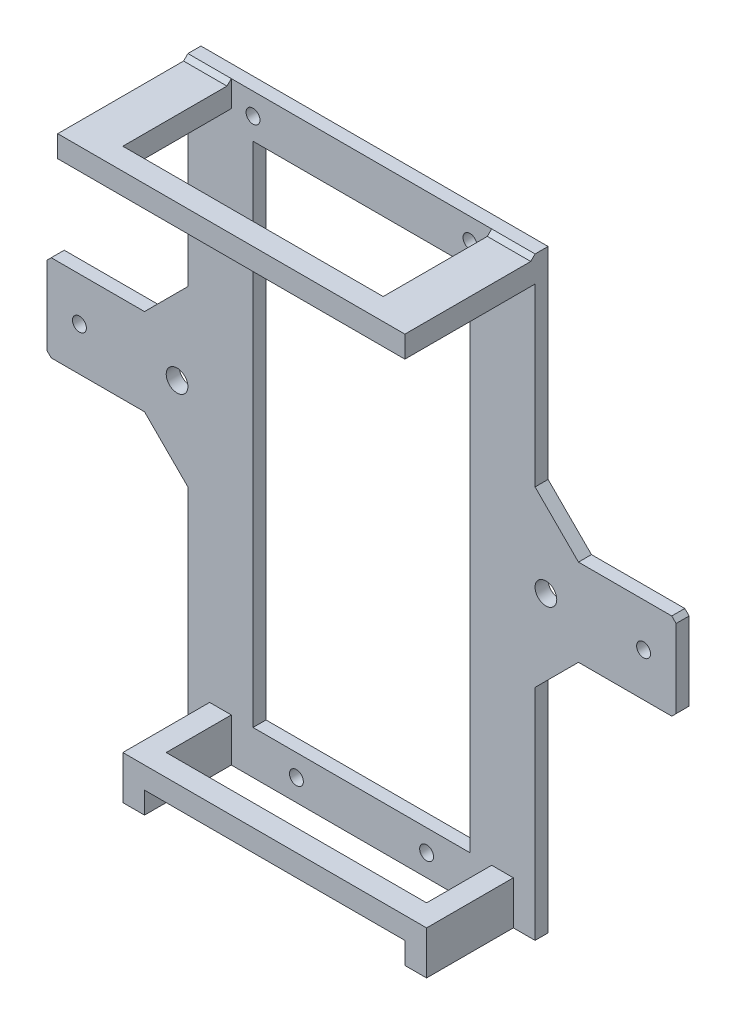
SolidWorks part; units mm, degrees
material "ABS"
ref_plane "前视基准面" through (0, 0, 0) normal (0, 0, 1) x (1, 0, 0)
ref_plane "上视基准面" through (0, 0, 0) normal (0, 1, 0) x (1, 0, 0)
ref_plane "右视基准面" through (0, 0, 0) normal (1, 0, 0) x (0, 0, -1)
other "Configuration Table"
sketch "草图9" plane through (0, 0, 0) normal (0, 0, 1) x (1, 0, 0)
  line L0 (-40, 66.5) -> (40, 66.5)
  line L1 (40, 66.5) -> (40, 10)
  line L2 (40, 10) -> (72.5, 10)
  line L3 (72.5, 10) -> (72.5, -10)
  line L4 (72.5, -10) -> (40, -10)
  line L5 (40, -10) -> (40, -70.5)
  line L6 (40, -70.5) -> (-40, -70.5)
  line L7 (0, 66.5) -> (0, -70.5) construction
  line L8 (-25, -60.5) -> (25, -60.5)
  line L9 (25, -60.5) -> (25, 56.5)
  line L10 (25, 56.5) -> (-25, 56.5)
  line L11 (-40, 61.5) -> (40, 61.5) construction
  line L12 (-40, -65.5) -> (40, -65.5) construction
  line L13 (72.5, 0) -> (-72.5, 0) construction
  line L14 (-25, -60.5) -> (-25, 56.5)
  line L15 (-40, -10) -> (-40, -70.5)
  line L16 (-72.5, -10) -> (-40, -10)
  line L17 (-72.5, 10) -> (-72.5, -10)
  line L18 (-40, 10) -> (-72.5, 10)
  line L19 (-40, 66.5) -> (-40, 10)
  circle A0 centre (25, 61.5) radius 1.6
  circle A1 centre (15, -65.5) radius 1.6
  circle A2 centre (42.5, 0) radius 2.5
  circle A3 centre (-42.5, 0) radius 2.5
  circle A4 centre (-15, -65.5) radius 1.6
  circle A5 centre (-25, 61.5) radius 1.6
  circle A6 centre (-65, 0) radius 1.6
  circle A7 centre (65, 0) radius 1.6
  point P26 (0, 0)
  point P27 (0, -65.5)
  point P28 (0, 61.5)
  point P35 (0, 56.5)
  point P36 (0, -60.5)
  dimension "D3" = 5
  dimension "D5" = 85
  dimension "D9" = 2.5
  dimension "D10" = 50
  dimension "D11" = 30
  dimension "D13" = 3.2
  dimension "D14" = 130
  dimension "D1" = 127
  dimension "D2" = 20
  dimension "D4" = 15
  dimension "D6" = 30
  dimension "D7" = 10
  dimension "D8" = 10
  dimension "D12" = 65.5
extrude "凸台-拉伸7" add sketch "草图9" along normal blind 3
sketch "草图10" plane through (0, 0, 3) normal (0, 0, 1) x (1, 0, 0)
  line L0 (0, 66.5) -> (0, 56.5) construction
  line L1 (-40, 65.5) -> (-30, 65.5)
  line L2 (-40, 65.5) -> (-40, 60.5)
  line L3 (-40, 60.5) -> (-30, 60.5)
  line L4 (-30, 65.5) -> (-30, 60.5)
  line L5 (40, 66.5) -> (-40, 66.5) construction
  line L6 (25, 56.5) -> (-25, 56.5) construction
  line L7 (40, 60.5) -> (30, 60.5)
  line L8 (30, 65.5) -> (30, 60.5)
  line L9 (40, 65.5) -> (30, 65.5)
  line L10 (40, 65.5) -> (40, 60.5)
  line L11 (-40, 66.5) -> (-40, 10) construction
  dimension "D1" = 10
  dimension "D2" = 5
  dimension "D3" = 1
extrude "凸台-拉伸8" add sketch "草图10" along normal blind 30
sketch "草图11" plane through (0, 0, 3) normal (0, 0, 1) x (1, 0, 0)
  line L1 (-35, -60.5) -> (-30, -60.5)
  line L2 (-35, -60.5) -> (-35, -70.5)
  line L3 (-35, -70.5) -> (-30, -70.5)
  line L4 (-30, -60.5) -> (-30, -70.5)
  line L5 (0, -60.5) -> (0, -70.5) construction
  line L6 (-25, -60.5) -> (25, -60.5) construction
  line L7 (-40, -70.5) -> (40, -70.5) construction
  line L8 (35, -70.5) -> (30, -70.5)
  line L9 (30, -60.5) -> (30, -70.5)
  line L10 (35, -60.5) -> (30, -60.5)
  line L11 (35, -60.5) -> (35, -70.5)
  dimension "D1" = 70
  dimension "D2" = 10
  dimension "D3" = 5
extrude "凸台-拉伸9" add sketch "草图11" along normal blind 20
sketch "草图12" plane through (0, 0, 33) normal (0, 0, 1) x (1, 0, 0)
  line L1 (-40, 65.5) -> (40, 65.5)
  line L2 (-40, 65.5) -> (-40, 60.5)
  line L3 (-40, 60.5) -> (40, 60.5)
  line L4 (40, 65.5) -> (40, 60.5)
extrude "凸台-拉伸10" add sketch "草图12" against normal blind 5
sketch "草图14" plane through (0, 0, 23) normal (0, 0, 1) x (1, 0, 0)
  line L0 (35, -70.5) -> (35, -60.5) construction
  line L1 (-35, -60.5) -> (35, -60.5)
  line L2 (-35, -60.5) -> (-35, -65.5)
  line L3 (-35, -65.5) -> (35, -65.5)
  line L4 (35, -60.5) -> (35, -65.5)
  dimension "D1" = 5
extrude "凸台-拉伸11" add sketch "草图14" against normal blind 5
chamfer "倒角2" distance 1 angle 45 6 edges at (35, 65.5, 3) (-35, 65.5, 3) (72.5, -10, 1.5) (72.5, 10, 1.5) (-72.5, -10, 1.5) (-72.5, 10, 1.5)
chamfer "倒角3" distance 10 angle 45 4 edges at (40, -10, 1.5) (40, 10, 1.5) (-40, -10, 1.5) (-40, 10, 1.5)
